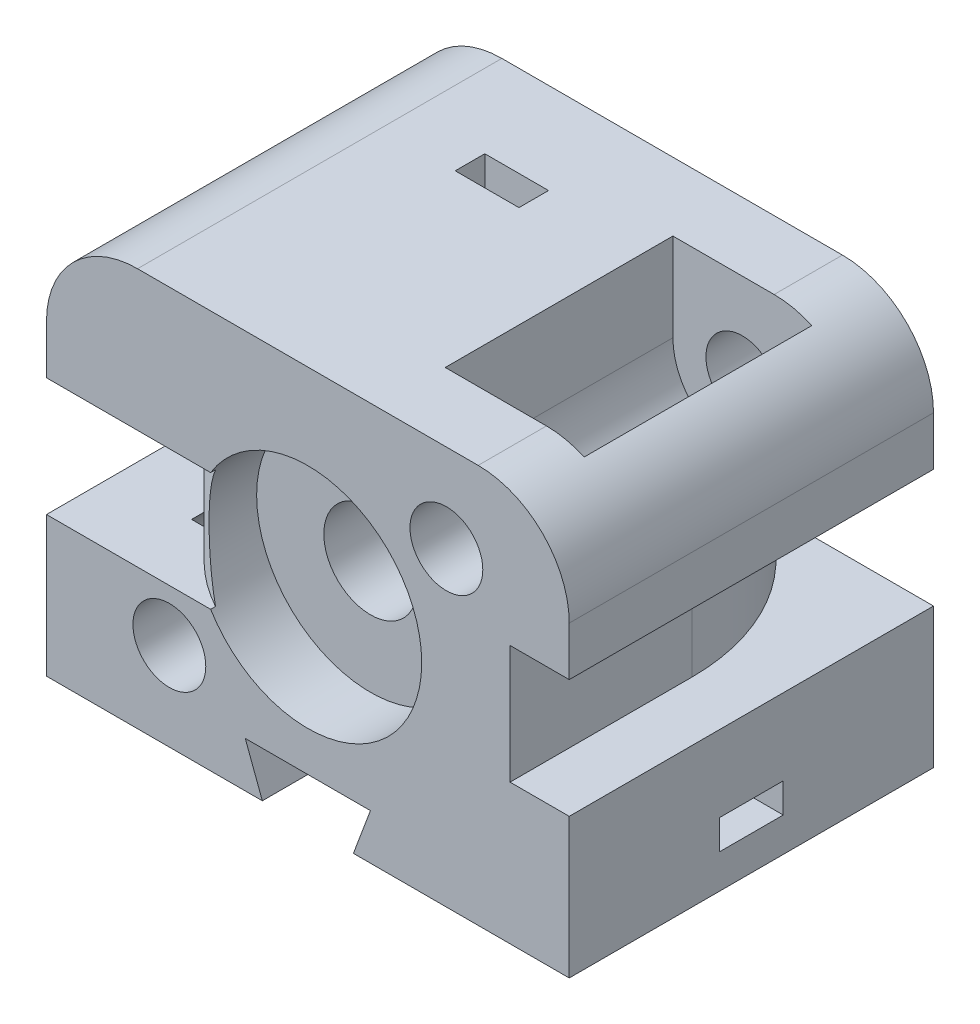
SolidWorks part; units mm, degrees
ref_plane "Front Plane" through (0, 0, 0) normal (0, 0, 1) x (1, 0, 0)
ref_plane "Top Plane" through (0, 0, 0) normal (0, 1, 0) x (1, 0, 0)
ref_plane "Right Plane" through (0, 0, 0) normal (1, 0, 0) x (0, 0, -1)
sketch "Sketch1" plane through (0, 0, 0) normal (0, 0, 1) x (1, 0, 0)
  line L0 (22.961, 13.5) -> (-22.961, 13.5) construction
  line L1 (-22.961, -17.5) -> (22.961, -17.5)
  line L2 (-22.961, -17.5) -> (-22.961, 17.5)
  line L3 (-22.961, 17.5) -> (22.961, 17.5)
  line L4 (22.961, -17.5) -> (22.961, 17.5)
  line L5 (-22.961, -17.5) -> (22.961, 17.5) construction
  line L6 (-22.961, 17.5) -> (22.961, -17.5) construction
  point P0 (0, 0)
  dimension "D1" = 35
extrude "Boss-Extrude1" add sketch "Sketch1" along normal mid plane 32
sketch "Sketch2" plane through (0, 0, 0) normal (0, 0, 1) x (1, 0, 0)
  circle A0 centre (0, 0) radius 4.1
  dimension "D1" = 8.2
extrude "Cut-Extrude1" cut sketch "Sketch2" against normal through all both and the other way through all
sketch "Sketch4" plane through (0, 0, 16) normal (0, 0, 1) x (1, 0, 0)
  line L0 (22.961, -17.5) -> (22.961, 17.5) construction
  line L1 (22.961, 5) -> (17.961, 5)
  line L2 (22.961, 5) -> (22.961, -5)
  line L3 (22.961, -5) -> (17.961, -5)
  line L4 (17.961, 5) -> (17.961, -5)
  line L5 (-22.961, 17.5) -> (-22.961, -17.5) construction
  line L6 (-22.961, 5) -> (-17.961, 5)
  line L7 (-22.961, 5) -> (-22.961, -5)
  line L8 (-22.961, -5) -> (-17.961, -5)
  line L9 (-17.961, 5) -> (-17.961, -5)
  line L10 (23.161, 5.2) -> (17.761, 5.2)
  line L11 (17.761, 5.2) -> (17.761, -5.2)
  line L12 (23.161, -5.2) -> (17.761, -5.2)
  line L13 (23.161, 5.2) -> (23.161, -5.2)
  line L14 (-23.161, 5.2) -> (-17.761, 5.2)
  line L15 (-17.761, 5.2) -> (-17.761, -5.2)
  line L16 (-23.161, -5.2) -> (-17.761, -5.2)
  line L17 (-23.161, 5.2) -> (-23.161, -5.2)
  line M6 (22.961, -17.5) -> (22.961, 17.5)
  line M8 (-22.961, 17.5) -> (-22.961, -17.5)
  dimension "D1" = 0.2
extrude "Cut-Extrude2" cut sketch "Sketch4" against normal up to next contours L1 L4 L3 M6 | L9 L6 L8 M8 | L12 L3 L4 L1 L10 L11 M6 | L16 L15 L14 L6 L9 L8 M8 region at (20.461, 0, 16) region at (20.461, 5.1163, 16) region at (-22.8447, 5.1, 16) region at (-20.461, 0, 16)
sketch "Sketch5" plane through (0, 0, 0) normal (0, 0, 1) x (1, 0, 0)
  line L0 (6.1674, 17.5) -> (6.1674, 9.7628)
  line L1 (18.1674, 9.7628) -> (18.1674, 17.5)
  line L2 (18.1674, 17.5) -> (6.1674, 17.5)
  line L3 (22.961, 17.5) -> (-22.961, 17.5) construction
  line L4 (18.2674, 9.7628) -> (18.2674, 17.6)
  line L5 (18.2674, 17.6) -> (6.0674, 17.6)
  line L6 (6.0674, 17.6) -> (6.0674, 9.7628)
  arc A0 (6.1674, 9.7628) -> (18.1674, 9.7628) centre (12.1674, 9.7628) ccw
  circle A3 centre (12.1674, 9.7628) radius 6 construction
  arc A4 (6.0674, 9.7628) -> (18.2674, 9.7628) centre (12.1674, 9.7628) ccw
  dimension "D1" = 0.1
extrude "Cut-Extrude3" cut sketch "Sketch5" against normal mid plane 20 contours L0 A0 L1 L2 | L6 A4 L4 L5 A0 L0 L2 L1 region at (12.1674, 11.2032, 0) region at (12.1674, 3.6814, 0)
sketch "Sketch6" plane through (0, 0, -16) normal (0, 0, -1) x (-1, 0, 0)
  circle A2 centre (0, 0) radius 11.2
  circle A3 centre (0, 0) radius 11.2
  dimension "D1" = 0.1
extrude "Cut-Extrude4" cut sketch "Sketch6" against normal blind 4
sketch "Sketch7" plane through (0, 0, -12) normal (0, 0, -1) x (-1, 0, 0)
  circle A4 centre (0, 0) radius 5.1
  circle A5 centre (0, 0) radius 5.1
  dimension "D1" = 0.1
extrude "Cut-Extrude5" cut sketch "Sketch7" against normal blind 10.5
pattern_circular "CirPattern1" count 2 over 360 about axis through (0, 0, -16) along (0, 0, -1) of "Cut-Extrude3"
sketch "Sketch8" plane through (0, 0, 0) normal (0, 0, 1) x (1, 0, 0)
  circle A16 centre (-12.1674, -9.7628) radius 3.2
  circle A17 centre (-12.1674, -9.7628) radius 3.2
  circle A19 centre (12.1674, 9.7628) radius 3.2
  circle A20 centre (12.1674, 9.7628) radius 3.2
  dimension "D1" = 0.2
  dimension "D2" = 0.2
extrude "Cut-Extrude6" cut sketch "Sketch8" against normal through all both and the other way through all
fillet "Fillet1" radius 8 2 edges at (22.961, 17.5, 0) (-22.961, 17.5, 0)
sketch "Sketch9" plane through (0, 0, -12) normal (0, 0, -1) x (-1, 0, 0)
  line L0 (2.8569, 7.2734) -> (2.8569, 17.5)
  line L1 (5.6569, 2.4237) -> (8.4569, 4.0403)
  line L2 (8.4569, 4.0403) -> (8.4569, 7.2734)
  line L3 (8.4569, 7.2734) -> (5.6569, 8.89)
  line L4 (5.6569, 8.89) -> (2.8569, 7.2734)
  line L5 (2.8569, 7.2734) -> (2.8569, 4.0403)
  line L6 (2.8569, 4.0403) -> (5.6569, 2.4237)
  line L7 (-14.961, 17.5) -> (14.961, 17.5) construction
  line L8 (2.8569, 17.5) -> (8.4569, 17.5)
  line L9 (8.4569, 17.5) -> (8.4569, 7.2734)
  circle A0 centre (5.6569, 5.6569) radius 2.8 construction
  circle M3 centre (0, 0) radius 5.1
  circle M4 centre (0, 0) radius 11.2
  dimension "D1" = 5.6
extrude "Cut-Extrude8" cut sketch "Sketch9" against normal blind 2.6 from offset 4 contours L9 L8 L0 M4 | L6 L1 L2 L3 L4 L5 M3 | L9 L0 L4 L3 M4 region at (-4.5212, 9.0571, -12) region at (-5.6647, 5.6621, -12) region at (-5.8545, 13.4272, -12) offset against normal yes
hole_wizard "M3 Clearance Hole1" positions "Sketch10" profile "Sketch11" hole size "M3" standard "ISO"
sketch "Sketch10" plane through (0, 0, -12) normal (0, 0, -1) x (-1, 0, 0)
  point P0 (5.6569, 5.6569)
sketch "Sketch11" plane through (-5.6569, 5.6569, -12) normal (1, 0, 0) x (0, 1, 0)
  line L0 (0, 0) -> (0, 11.0215)
  line L1 (0, 11.0215) -> (1.7, 10)
  line L2 (1.7, 10) -> (1.7, 0)
  line L5 (1.7, 0) -> (0, 0)
  line L10 (0, 11.0215) -> (-1.7, 10) construction
  line L11 (0, -6.35) -> (0, 107.95) construction
  dimension "Hole Dia." = 3.4
  dimension "Hole Depth" = 10
  dimension "Drill Angle" = 118
pattern_circular "CirPattern2" count 2 over 360 about axis through (0, 0, -16) along (0, 0, -1) of "Cut-Extrude8", "M3 Clearance Hole1"
sketch "Sketch13" plane through (0, 0, 0) normal (0, 0, 1) x (1, 0, 0)
  line L0 (0, 0) -> (0, 14.9036) construction
  line L1 (17.761, -5.2) -> (50, -5.2)
  line L2 (17.761, -5.2) -> (17.761, 5.2)
  line L3 (17.761, 5.2) -> (50, 5.2)
  line L4 (50, -5.2) -> (50, 5.2)
  line L5 (-17.761, -5.2) -> (-50, -5.2)
  line L6 (-17.761, -5.2) -> (-17.761, 5.2)
  line L7 (-17.761, 5.2) -> (-50, 5.2)
  line L8 (-50, -5.2) -> (-50, 5.2)
  line L9 (22.961, 5.2) -> (17.761, 5.2) construction
  line L10 (-22.961, 5.2) -> (-17.761, 5.2) construction
  dimension "D1" = 100
revolve "Cut-Revolve1" cut sketch "Sketch13" angle 90 about L0
sketch "Sketch14" plane through (0, 0, 16) normal (0, 0, 1) x (1, 0, 0)
  circle A0 centre (0, 0) radius 10
  dimension "D1" = 20
extrude "Cut-Extrude9" cut sketch "Sketch14" against normal blind 5.5
sketch "Sketch15" plane through (0, 0, 16) normal (0, 0, 1) x (1, 0, 0)
  line L0 (-4, -17.5) -> (-5.5, -13.5)
  line L1 (-22.961, -17.5) -> (22.961, -17.5) construction
  line L2 (-5.5, -13.5) -> (5.5, -13.5)
  line L3 (5.5, -13.5) -> (4, -17.5)
  line L4 (4, -17.5) -> (-4, -17.5)
  point P4 (0, -17.5)
  point P7 (0, -13.5)
  dimension "D1" = 8
  dimension "D2" = 11
  dimension "D3" = 4
extrude "Cut-Extrude10" cut sketch "Sketch15" against normal through all
sketch "Sketch16" plane through (0, -17.5, 0) normal (0, -1, 0) x (1, 0, 0)
  line L0 (19.6166, -2.8) -> (22.961, -2.8)
  line L1 (19.6166, 2.8) -> (16.3834, 2.8)
  line L2 (16.3834, 2.8) -> (14.7668, 0)
  line L3 (14.7668, 0) -> (16.3834, -2.8)
  line L4 (16.3834, -2.8) -> (19.6166, -2.8)
  line L5 (19.6166, -2.8) -> (21.2332, 0)
  line L6 (21.2332, 0) -> (19.6166, 2.8)
  line L7 (22.961, 16) -> (22.961, -16) construction
  line L8 (22.961, -2.8) -> (22.961, 2.8)
  line L9 (22.961, 2.8) -> (19.6166, 2.8)
  circle A0 centre (18, 0) radius 2.8 construction
  line M14 (22.961, -16) -> (22.961, 16)
  dimension "D1" = 5.6
  dimension "D2" = 18
extrude "Cut-Extrude11" cut sketch "Sketch16" against normal blind 2.6 from offset 3 contours L5 L6 L1 L2 L3 L4 | L9 L6 L5 L0 M14 region at (21.65, -17.5, 0) region at (18, -17.5, 0) offset against normal yes
hole_wizard "M3 Clearance Hole2" positions "Sketch17" profile "Sketch18" hole size "M3" standard "ISO"
sketch "Sketch17" plane through (0, -17.5, 0) normal (0, -1, 0) x (-1, 0, 0)
  line L0 (-16.3834, -2.8) -> (-14.7668, 0) construction
  line L1 (-14.7668, 0) -> (-16.3834, 2.8) construction
  line L2 (-22.961, -2.8) -> (-16.3834, -2.8) construction
  circle A0 centre (-18, 0) radius 2.8
  point P0 (-18, 0)
sketch "Sketch18" plane through (18, -17.5, 0) normal (1, 0, 0) x (0, 0, -1)
  line L0 (0, 0) -> (0, 11.0215)
  line L1 (0, 11.0215) -> (1.7, 10)
  line L2 (1.7, 10) -> (1.7, 0)
  line L5 (1.7, 0) -> (0, 0)
  line L10 (0, 11.0215) -> (-1.7, 10) construction
  line L11 (0, -6.35) -> (0, 107.95) construction
  dimension "Hole Dia." = 3.4
  dimension "Hole Depth" = 10
  dimension "Drill Angle" = 118
